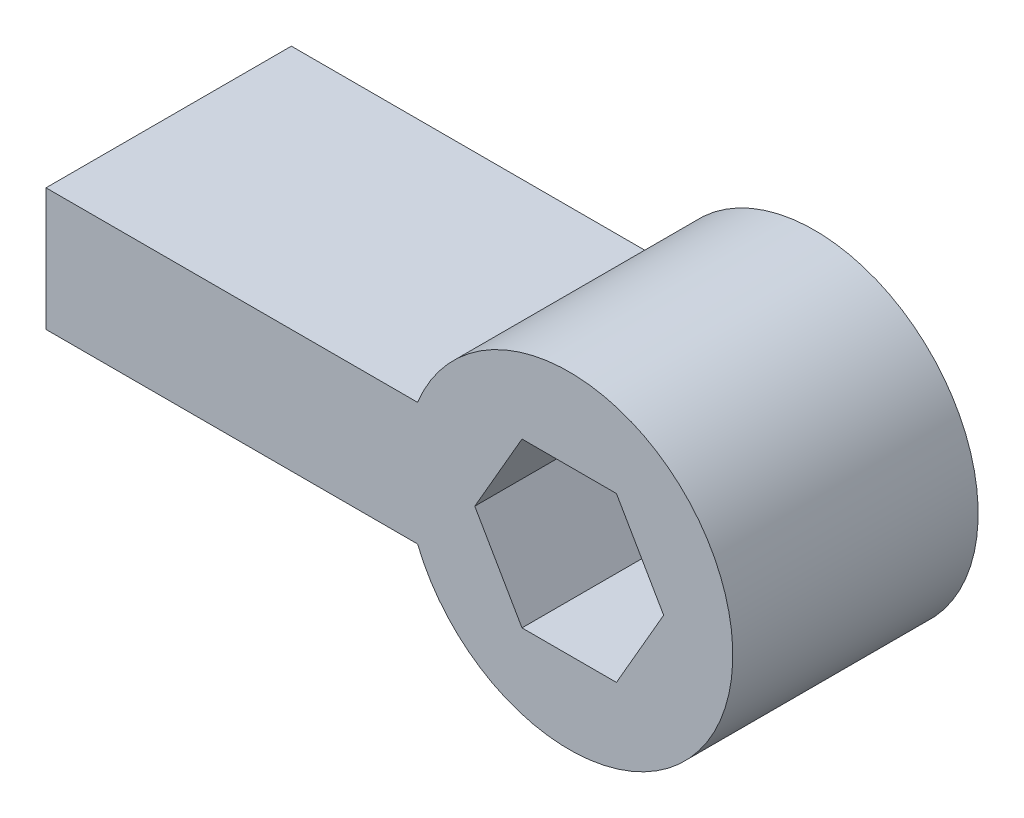
SolidWorks part; units mm, degrees
ref_plane "Front Plane" through (0, 0, 0) normal (0, 0, 1) x (1, 0, 0)
ref_plane "Top Plane" through (0, 0, 0) normal (0, 1, 0) x (1, 0, 0)
ref_plane "Right Plane" through (0, 0, 0) normal (1, 0, 0) x (0, 0, -1)
sketch "Sketch1" plane through (0, 0, 0) normal (0, 0, 1) x (1, 0, 0)
  line L0 (4.3947, 0) -> (6.7041, 0)
  line L1 (5.5494, 0) -> (5.5494, 2) construction
  line L3 (4.3947, 4) -> (3.24, 2)
  line L4 (6.7041, 4) -> (4.3947, 4)
  line L5 (7.8588, 2) -> (6.7041, 4)
  line L6 (6.7041, 0) -> (7.8588, 2)
  line L8 (3.24, 2) -> (4.3947, 0)
  line L9 (1.0426, 5.8059) -> (2.0853, 4) [skipped]
  circle A0 centre (5.5494, 2) radius 4
  point P17 (5.5494, 2)
  dimension "D2" = 4
  dimension "D5" = 8
  dimension "D1" = 6
  dimension "D3" = 4
  dimension "D4" = 4
extrude "Boss-Extrude1" add sketch "Sketch1" along normal blind 6
ref_plane "Plane1" through (0, 2, 0) normal (0, 1, 0) x (1, 0, 0)
sketch "Sketch2" plane through (0, 2, 0) normal (0, 1, 0) x (1, 0, 0)
  line L0 (3.24, 0) -> (1.5494, 0)
  line L2 (1.5494, -6) -> (3.24, -6)
  line L3 (1.5494, -6) -> (9.5494, -6) construction
  line L4 (3.24, -6) -> (3.24, 0)
  line L6 (1.5494, 0) -> (-7.2453, 0)
  line L7 (-7.2453, -6) -> (1.5494, -6)
  line L8 (-7.2453, 0) -> (-7.2453, -6)
extrude "Boss-Extrude2" add sketch "Sketch2" along normal blind 1.5 and the other way blind 1.5
